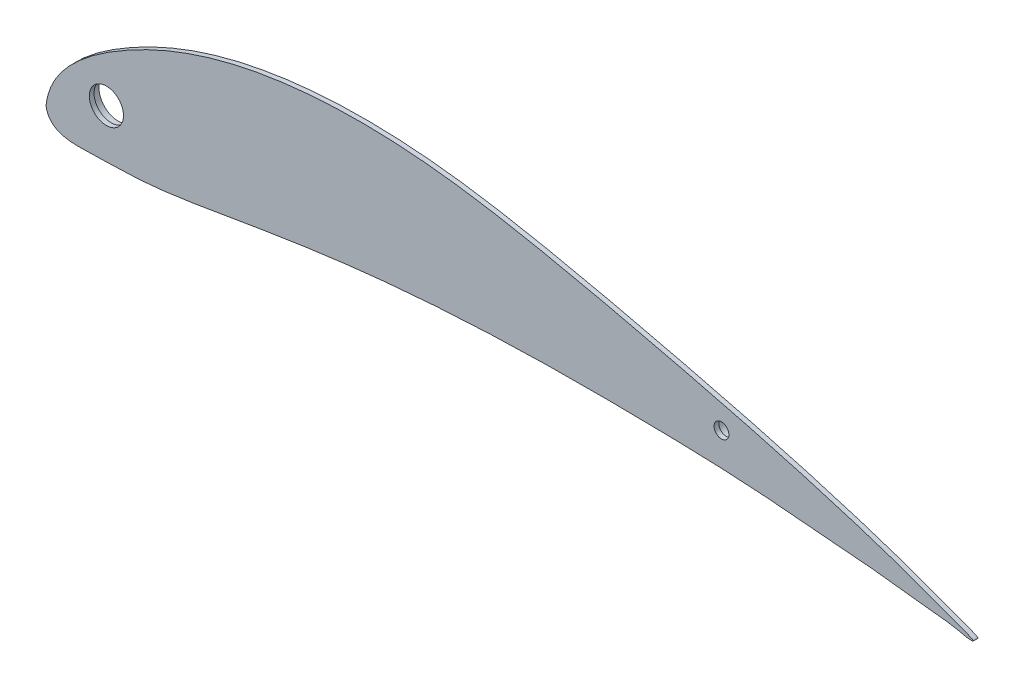
SolidWorks part; units mm, degrees
material "ABS"
ref_plane "Front Plane" through (0, 0, 0) normal (0, 0, 1) x (1, 0, 0)
ref_plane "Top Plane" through (0, 0, 0) normal (0, 1, 0) x (1, 0, 0)
ref_plane "Right Plane" through (0, 0, 0) normal (1, 0, 0) x (0, 0, -1)
sketch "Sketch1" plane through (0, 0, 0) normal (0, 0, 1) x (1, 0, 0)
  spline S0 degree 3 poles (0.0006, 0.0001) (0.8106, 7.3592) (8.6491, 17.8566) (26.2867, 29.9752) (52.1111, 42.0692) (89.5976, 49.2908) (131.4008, 47.8848) (173.2567, 40.0411) (217.9611, 29.613) (256.9521, 19.5289) (290.3598, 8.711) (301.2732, 4.3828) (314.8169, -0.5162) (309.8463, 0.0001) knots 0 0 0 0 0.060864 0.113688 0.188609 0.312909 0.448482 0.557612 0.691544 0.852438 0.929756 0.976058 1 1 1 1
  spline S1 degree 3 poles (309.8463, 0.0001) (303.9568, 1.471) (293.9895, 2.094) (276.264, 4.5144) (260.8463, 5.4274) (235.8588, 7.8703) (205.1014, 8.8381) (157.7186, 9.0307) (110.4973, 6.1815) (66.5062, -0.5867) (36.4547, -6.0985) (15.3166, -6.1891) (1.2307, -6.9241) (0.0006, 0.0001) knots 0 0 0 0 0.057787 0.095275 0.171021 0.205339 0.335319 0.464904 0.658702 0.785512 0.893517 0.943092 1 1 1 1
extrude "Boss-Extrude1" add sketch "Sketch1" along normal blind 1.5875
sketch "Sketch2" plane through (0, 0, 1.5875) normal (0, 0, 1) x (1, 0, 0)
  circle A0 centre (20.32, 10.16) radius 6.5
  circle A1 centre (227.2963, 19.0501) radius 3
  circle A2 centre (20.32, 10.16) radius 5.75
  circle A3 centre (20.32, 10.16) radius 8
  circle A4 centre (227.2963, 19.0501) radius 4.5
  circle A5 centre (227.2963, 19.0501) radius 2.5
  dimension "D2" = 13
  dimension "D3" = 6
  dimension "D6" = 20.32
  dimension "D7" = 1.5
  dimension "D8" = 11.5
  dimension "D9" = 5
  dimension "D10" = 1.5
  dimension "D1" = 82.55
  dimension "D4" = 19.05
  dimension "D5" = 10.16
extrude "Boss-Extrude2" add sketch "Sketch2" against normal blind 4 contours A4 A1 | A3 A0 region at (12.5463, 10.16, 1.5875) region at (222.9236, 19.0501, 1.5875)
extrude "Cut-Extrude1" cut sketch "Sketch2<4>" against normal blind 4 contours A5 | A2 region at (20.32, 10.16, 1.5875) region at (227.2963, 19.0501, 1.5875)
sketch "Sketch2<4>" plane through (0, 0, 1.5875) normal (0, 0, 1) x (1, 0, 0) same geometry as "Sketch2"
